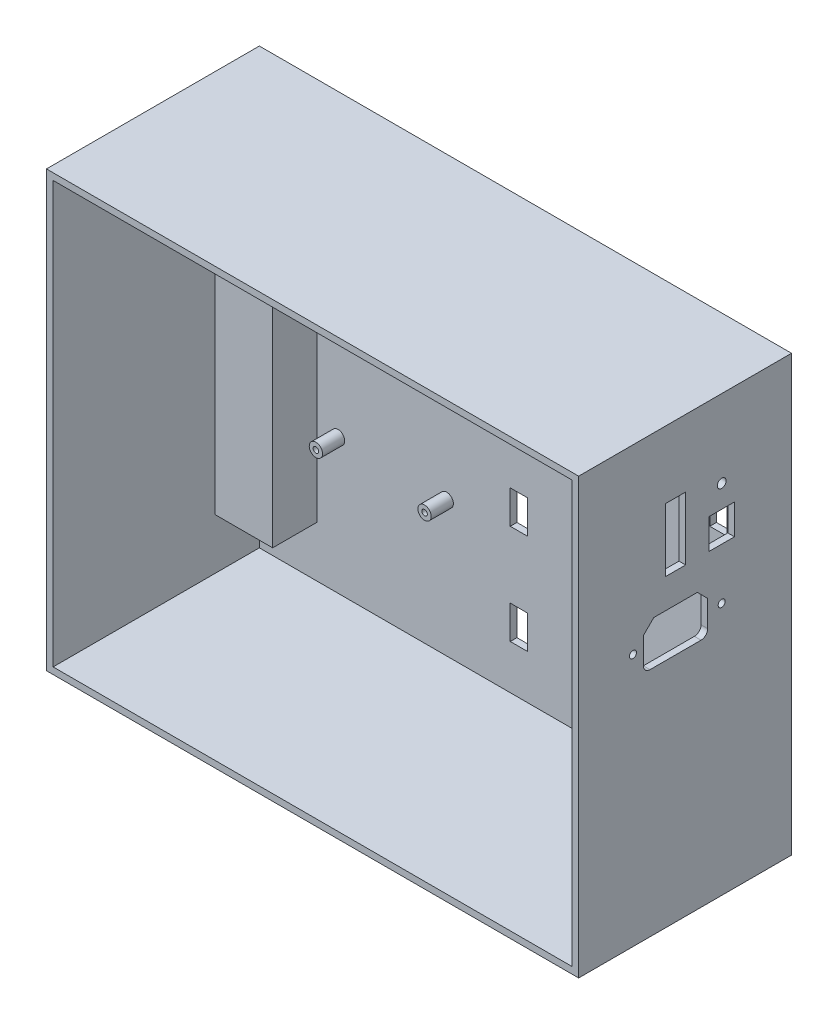
SolidWorks part; units mm, degrees
ref_plane "Front Plane" through (0, 0, 0) normal (0, 0, 1) x (1, 0, 0)
ref_plane "Top Plane" through (0, 0, 0) normal (0, 1, 0) x (1, 0, 0)
ref_plane "Right Plane" through (0, 0, 0) normal (1, 0, 0) x (0, 0, -1)
sketch "Sketch1" plane through (0, 0, 0) normal (0, 0, 1) x (1, 0, 0)
  line L1 (117, 95) -> (-117, 95)
  line L2 (117, 95) -> (117, -95)
  line L3 (117, -95) -> (-117, -95)
  line L4 (-117, 95) -> (-117, -95)
  line L5 (117, 95) -> (-117, -95) construction
  line L6 (117, -95) -> (-117, 95) construction
  point P0 (0, 0)
  dimension "D1" = 234
  dimension "D2" = 190
extrude "Boss-Extrude1" add sketch "Sketch1" along normal blind 3
sketch "Sketch2" plane through (0, 0, 3) normal (0, 0, 1) x (1, 0, 0)
  line L4 (-117, 95) -> (-117, -95)
  line L5 (-117, -95) -> (117, -95)
  line L6 (117, -95) -> (117, 95)
  line L7 (117, 95) -> (-117, 95)
  line L8 (-117, 95) -> (-117, -95)
  line L9 (-117, -95) -> (117, -95)
  line L10 (117, -95) -> (117, 95)
  line L11 (117, 95) -> (-117, 95)
  dimension "D1" = 0
extrude "Extrude-Thin1" add sketch "Sketch2" along normal blind 93 and the other way blind 3 thin thin type one direction wall 3
sketch "Sketch3" plane through (0, 0, 0) normal (0, 0, -1) x (-1, 0, 0)
  line L0 (-120, 0) -> (120, 0) construction
  line L1 (-120, -98) -> (-120, 98) construction
  line L2 (120, 98) -> (120, -98) construction
  line L3 (-56.15, 30) -> (-56.15, 15)
  line L4 (-93.85, 30) -> (-86.15, 30)
  line L5 (-93.85, 30) -> (-93.85, 15)
  line L6 (-93.85, 15) -> (-86.15, 15)
  line L7 (-86.15, 30) -> (-86.15, 15)
  line L8 (-93.85, 30) -> (-86.15, 15) construction
  line L9 (-93.85, 15) -> (-86.15, 30) construction
  line L10 (-63.85, 15) -> (-56.15, 15)
  line L11 (-63.85, 30) -> (-63.85, 15)
  line L12 (-63.85, 30) -> (-56.15, 30)
  line L13 (-26.15, 30) -> (-26.15, 15)
  line L14 (-33.85, 15) -> (-26.15, 15)
  line L15 (-33.85, 30) -> (-33.85, 15)
  line L16 (-33.85, 30) -> (-26.15, 30)
  line L17 (3.85, 30) -> (3.85, 15)
  line L18 (-3.85, 15) -> (3.85, 15)
  line L19 (-3.85, 30) -> (-3.85, 15)
  line L20 (-3.85, 30) -> (3.85, 30)
  line L21 (-56.15, 75) -> (-56.15, 60)
  line L22 (-63.85, 60) -> (-56.15, 60)
  line L23 (-63.85, 75) -> (-63.85, 60)
  line L24 (-63.85, 75) -> (-56.15, 75)
  line L25 (-26.15, 75) -> (-26.15, 60)
  line L26 (-33.85, 60) -> (-26.15, 60)
  line L27 (-33.85, 75) -> (-33.85, 60)
  line L28 (-33.85, 75) -> (-26.15, 75)
  line L29 (3.85, 75) -> (3.85, 60)
  line L30 (-3.85, 60) -> (3.85, 60)
  line L31 (-3.85, 75) -> (-3.85, 60)
  line L32 (-3.85, 75) -> (3.85, 75)
  line L33 (-86.15, 75) -> (-86.15, 60)
  line L34 (-93.85, 60) -> (-86.15, 60)
  line L35 (-93.85, 75) -> (-93.85, 60)
  line L36 (-93.85, 75) -> (-86.15, 75)
  line L37 (-93.85, -15) -> (-86.15, -30) construction
  line L38 (-93.85, -30) -> (-86.15, -15) construction
  line L39 (-93.85, -75) -> (-86.15, -75)
  line L40 (-93.85, -75) -> (-93.85, -60)
  line L41 (-93.85, -60) -> (-86.15, -60)
  line L42 (-86.15, -75) -> (-86.15, -60)
  line L43 (-3.85, -75) -> (3.85, -75)
  line L44 (-3.85, -75) -> (-3.85, -60)
  line L45 (-3.85, -60) -> (3.85, -60)
  line L46 (3.85, -75) -> (3.85, -60)
  line L47 (-33.85, -75) -> (-26.15, -75)
  line L48 (-33.85, -75) -> (-33.85, -60)
  line L49 (-33.85, -60) -> (-26.15, -60)
  line L50 (-26.15, -75) -> (-26.15, -60)
  line L51 (-63.85, -75) -> (-56.15, -75)
  line L52 (-63.85, -75) -> (-63.85, -60)
  line L53 (-63.85, -60) -> (-56.15, -60)
  line L54 (-56.15, -75) -> (-56.15, -60)
  line L55 (-3.85, -30) -> (3.85, -30)
  line L56 (-3.85, -30) -> (-3.85, -15)
  line L57 (-3.85, -15) -> (3.85, -15)
  line L58 (3.85, -30) -> (3.85, -15)
  line L59 (-33.85, -30) -> (-26.15, -30)
  line L60 (-33.85, -30) -> (-33.85, -15)
  line L61 (-33.85, -15) -> (-26.15, -15)
  line L62 (-26.15, -30) -> (-26.15, -15)
  line L63 (-63.85, -30) -> (-56.15, -30)
  line L64 (-63.85, -30) -> (-63.85, -15)
  line L65 (-63.85, -15) -> (-56.15, -15)
  line L66 (-86.15, -30) -> (-86.15, -15)
  line L67 (-93.85, -15) -> (-86.15, -15)
  line L68 (-93.85, -30) -> (-93.85, -15)
  line L69 (-93.85, -30) -> (-86.15, -30)
  line L70 (-56.15, -30) -> (-56.15, -15)
  point P6 (-90, 22.5)
  point P71 (-90, -22.5)
  dimension "D1" = 45
  dimension "D2" = 15
  dimension "D3" = 7.7
  dimension "D4" = 30
  dimension "D5" = 4
  dimension "D6" = 2
extrude "Cut-Extrude1" cut sketch "Sketch3" against normal up to surface (3 mm away) up to face at (0, 0, 3)
sketch "Sketch4" plane through (120, 0, 0) normal (1, 0, 0) x (0, 0, -1)
  line L0 (-52.2967, -9.5511) -> (-52.2967, 82.4489) construction
  line L1 (-86.3289, 16.0927) -> (-18.2646, 16.0927) construction
  line L2 (-42.4831, 25.8427) -> (-37.7967, 21.1563)
  line L3 (-63.7967, 6.3427) -> (-40.7967, 6.3427)
  line L4 (-66.7967, 9.3427) -> (-66.7967, 21.1563)
  line L5 (-62.1104, 25.8427) -> (-42.4831, 25.8427)
  line L6 (-37.7967, 9.3427) -> (-37.7967, 21.1563)
  line L7 (-66.7967, 6.3427) -> (-37.7967, 25.8427) construction
  line L8 (-66.7967, 25.8427) -> (-37.7967, 6.3427) construction
  line L9 (-66.7967, 21.1563) -> (-62.1104, 25.8427)
  line L10 (-56.8558, 39.1939) -> (-47.7377, 39.1939)
  line L11 (-56.8558, 39.1939) -> (-56.8558, 67.6877)
  line L12 (-56.8558, 67.6877) -> (-47.7377, 67.6877)
  line L13 (-47.7377, 39.1939) -> (-47.7377, 67.6877)
  line L14 (-56.8558, 39.1939) -> (-47.7377, 67.6877) construction
  line L15 (-56.8558, 67.6877) -> (-47.7377, 39.1939) construction
  line L16 (-37.2405, 39.1939) -> (-25.7438, 39.1939)
  line L17 (-37.2405, 39.1939) -> (-37.2405, 52.8039)
  line L18 (-37.2405, 52.8039) -> (-25.7438, 52.8039)
  line L19 (-25.7438, 39.1939) -> (-25.7438, 52.8039)
  line L20 (-37.2405, 39.1939) -> (-25.7438, 52.8039) construction
  line L21 (-37.2405, 52.8039) -> (-25.7438, 39.1939) construction
  circle A0 centre (-31.4921, 16.0927) radius 1.6
  circle A1 centre (-71.4921, 16.0927) radius 1.6
  arc A2 (-63.7967, 6.3427) -> (-66.7967, 9.3427) centre (-63.7967, 9.3427) cw
  arc A3 (-40.7967, 6.3427) -> (-37.7967, 9.3427) centre (-40.7967, 9.3427) ccw
  circle A4 centre (-31.4921, 62.9489) radius 2
  point P5 (-52.2967, 16.0927)
  point P9 (-52.2967, 16.0927)
  point P24 (-52.2967, 53.4408)
  point P29 (-31.4921, 45.9989)
  point P38 (-52.2967, 25.8427)
extrude "Cut-Extrude2" cut sketch "Sketch4" against normal up to surface (3 mm away) up to face at (117, 0, 49.5)
sketch "Sketch5" plane through (0, 0, 3) normal (0, 0, 1) x (1, 0, 0)
  line L0 (-117, 95) -> (-117, -95) construction
  line L1 (-32.5, 24) -> (-81.5, 24) construction
  line L2 (-32.5, 24) -> (-32.5, -34) construction
  line L3 (-32.5, -34) -> (-81.5, -34) construction
  line L4 (-81.5, 24) -> (-81.5, -34) construction
  line L5 (-32.5, 24) -> (-81.5, -34) construction
  line L6 (-32.5, -34) -> (-81.5, 24) construction
  line L7 (117, 95) -> (-117, 95) construction
  circle A0 centre (-81.5, 24) radius 1.25
  circle A1 centre (-32.5, 24) radius 1.25
  circle A2 centre (-81.5, -34) radius 1.25
  circle A3 centre (-32.5, -34) radius 1.25
  circle A4 centre (-81.5, 24) radius 3
  circle A5 centre (-32.5, 24) radius 3
  circle A6 centre (-81.5, -34) radius 3
  circle A7 centre (-32.5, -34) radius 3
  point P0 (-57, -5)
  dimension "D3" = 2.5
  dimension "D4" = 6
  dimension "D1" = 49
  dimension "D2" = 58
  dimension "D5" = 60
  dimension "D6" = 100
extrude "Boss-Extrude2" add sketch "Sketch5" along normal blind 10
sketch "Sketch6" plane through (0, 0, 3) normal (0, 0, 1) x (1, 0, 0)
  line L0 (-3.85, 67.5) -> (3.85, 67.5) construction
  line L1 (-3.85, 75) -> (-3.85, 60) construction
  line L2 (3.85, 60) -> (3.85, 75) construction
  circle A0 centre (0, 79.5) radius 1.4
  circle A1 centre (0, 79.5) radius 3
  circle A2 centre (46, 79.5) radius 3
  circle A3 centre (46, 79.5) radius 1.4
  circle A4 centre (96, 79.5) radius 3
  circle A5 centre (96, 79.5) radius 1.4
  dimension "D1" = 2.8
  dimension "D2" = 6
  dimension "D4" = 2
  dimension "D3" = 12
  dimension "D5" = 2
sketch "Sketch7" plane through (0, 0, 3) normal (0, 0, 1) x (1, 0, 0)
  line L0 (-117, 0) -> (-91, 0) construction
  line L1 (-117, 95) -> (-117, -95) construction
  line L3 (-91, 72) -> (-117, 72)
  line L4 (-91, 72) -> (-91, -72)
  line L5 (-91, -72) -> (-117, -72)
  line L6 (-117, 72) -> (-117, -72)
  line L7 (-91, 72) -> (-117, -72) construction
  line L8 (-91, -72) -> (-117, 72) construction
  point P5 (-104, 0)
  dimension "D1" = 26
  dimension "D2" = 144
extrude "Boss-Extrude3" add sketch "Sketch7" along normal blind 20
sketch "Sketch8" plane through (0, 0, 0) normal (0, 0, -1) x (-1, 0, 0)
  line L0 (120, 0) -> (55.0521, 0) construction
  line L1 (120, 98) -> (120, -98) construction
  line L3 (117, 70.25) -> (91.8, 70.25)
  line L4 (117, 70.25) -> (117, -70.25)
  line L5 (117, -70.25) -> (91.8, -70.25)
  line L6 (91.8, 70.25) -> (91.8, -70.25)
  line L7 (117, 70.25) -> (91.8, -70.25) construction
  line L8 (117, -70.25) -> (91.8, 70.25) construction
  point P5 (104.4, 0)
  dimension "D1" = 3
  dimension "D2" = 25.2
  dimension "D3" = 140.5
extrude "Cut-Extrude3" cut sketch "Sketch8" against normal blind 18
